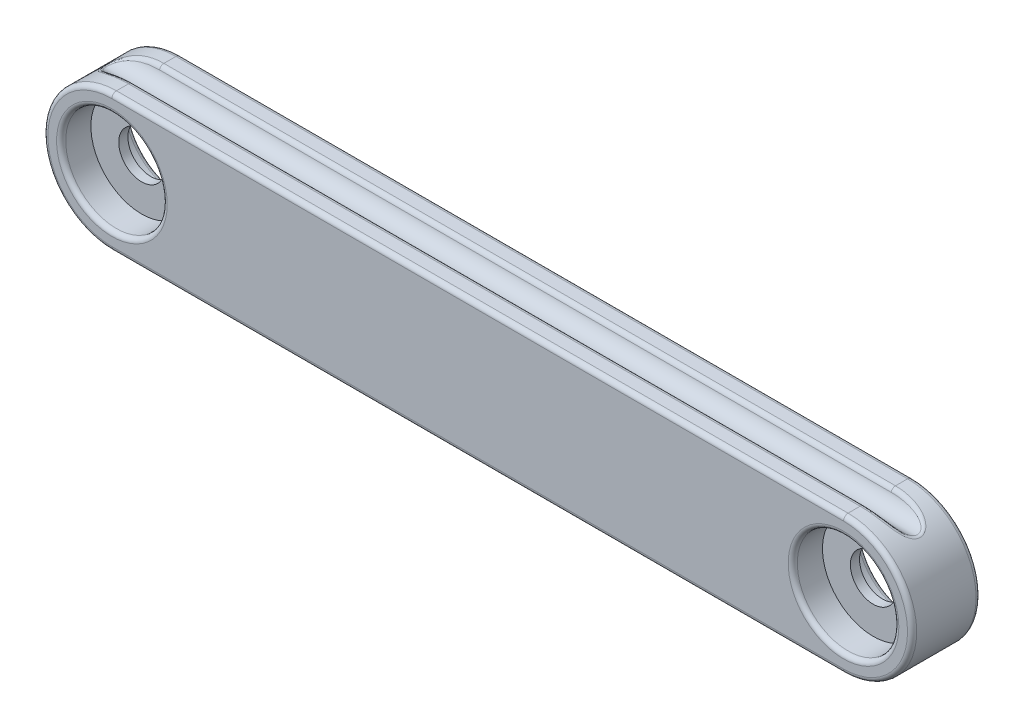
SolidWorks part; units mm, degrees
ref_plane "Front Plane" through (0, 0, 0) normal (0, 0, 1) x (1, 0, 0)
ref_plane "Top Plane" through (0, 0, 0) normal (0, 1, 0) x (1, 0, 0)
ref_plane "Right Plane" through (0, 0, 0) normal (1, 0, 0) x (0, 0, -1)
ref_axis "X" through (-88.99, 0, 0) along (1, 0, 0)
ref_axis "Y" through (0, 55, 0) along (0, -1, 0)
ref_axis "Z" through (0, 0, -88.99) along (0, 0, 1)
sketch "Sketch1" plane through (0, 0, 0) normal (0, 0, 1) x (1, 0, 0)
  line L0 (-80, 0) -> (80, 0) construction
  line L2 (-80, 15) -> (80, 15)
  line L3 (-80, -15) -> (80, -15)
  arc A0 (-80, 15) -> (-80, -15) centre (-80, 0) ccw
  arc A1 (80, -15) -> (80, 15) centre (80, 0) ccw
  circle A2 centre (80, 0) radius 11.1
  circle A3 centre (-80, 0) radius 11.1
  circle A4 centre (-80, 0) radius 5
  circle A5 centre (80, 0) radius 5
  point P5 (0, 0)
  dimension "D2" = 15
  dimension "D3" = 22.2
  dimension "D4" = 10
  dimension "D1" = 160
extrude "Boss-Extrude1" add sketch "Sketch1" along normal mid plane 2 contours L3 A1 L2 A0 A3 A2 | A4 A3 | A2 A5 region at (0, 0, 0) region at (69.214, 0, 0) region at (-90.786, 0, 0)
extrude "Boss-Extrude2" add sketch "Sketch1<3>" along normal mid plane 15 contours L3 A1 L2 A0 A3 A2 region at (0, 0, 0)
sketch "Sketch1<3>" plane through (0, 0, 0) normal (0, 0, 1) x (1, 0, 0) same geometry as "Sketch1"
sketch "Sketch2" plane through (0, 0, 0) normal (1, 0, 0) x (0, 0, -1)
  line L0 (-7.5, 15) -> (7.5, 15) construction
  line L1 (-7.5, 15) -> (7.5, 15)
  arc A0 (-3, 15) -> (3, 15) centre (0, 15) ccw
  point P6 (0, 15)
  dimension "D1" = 3
extrude "Cut-Extrude1" cut sketch "Sketch2" against normal through all both and the other way through all contours L1 A0 region at (0, 13.7268, 0)
fillet "Fillet1" radius 1 4 edges at (-88.9935, 12.0049, -0.1707) (0, 15, 3) (88.9935, 12.0049, 0.1707) (0, 15, -3)
mirror "Mirror3" [suppressed] about plane through (0, 0, 0) normal (0, 1, 0)
sketch "Sketch3" [suppressed] plane through (0, 0, 1) normal (0, 0, 1) x (1, 0, 0)
  circle A1 centre (80, 0) radius 11.1
  circle A2 centre (80, 0) radius 11.1
  circle A3 centre (80, 0) radius 5 construction
  circle A4 centre (80, 0) radius 5
  dimension "D1" = 0
extrude "Boss-Extrude3" [suppressed] add sketch "Sketch3" along normal up to surface (6.5 mm away) up to face at (91.1, 0, 7.5)
fillet "Fillet2" radius 1 12 edges at (-95, 0, 7.5) (0, 15, 7.5) (95, 0, 7.5) (0, -15, 7.5) (-68.9, 0, 7.5) (91.1, 0, 7.5) (95, 0, -7.5) (0, 15, -7.5) (-95, 0, -7.5) (0, -15, -7.5) (-68.9, 0, -7.5) (91.1, 0, -7.5)
mirror "Mirror1" [suppressed] about plane through (0, 0, 0) normal (1, 0, 0) of bodies 104
delete or keep bodies "Body-Delete/Keep 1" [suppressed] type keep bodies bodies 105
sketch "Sketch4" [suppressed] plane through (0, 0, 7.5) normal (0, 0, 1) x (1, 0, 0)
  circle A0 centre (70.25, 0) radius 0.75 construction
  circle A1 centre (67.25, 0) radius 0.75 construction
  circle A2 centre (64.25, 0) radius 0.75 construction
  circle A3 centre (61.25, 0) radius 0.75 construction
  circle A4 centre (70.25, 0) radius 0.75 construction
  circle A5 centre (67.25, 0) radius 0.75 construction
  circle A6 centre (64.25, 0) radius 0.75 construction
  circle A7 centre (61.25, 0) radius 0.75 construction
  circle A8 centre (61.25, 0) radius 0.6
  circle A9 centre (64.25, 0) radius 0.6
  circle A10 centre (67.25, 0) radius 0.6
  circle A11 centre (70.25, 0) radius 0.6
  dimension "D1" = 1.2
extrude "Cut-Extrude2" [suppressed] cut sketch "Sketch4" against normal offset from surface (6.5 mm away) 2 up to face at (85, 0, -1)
